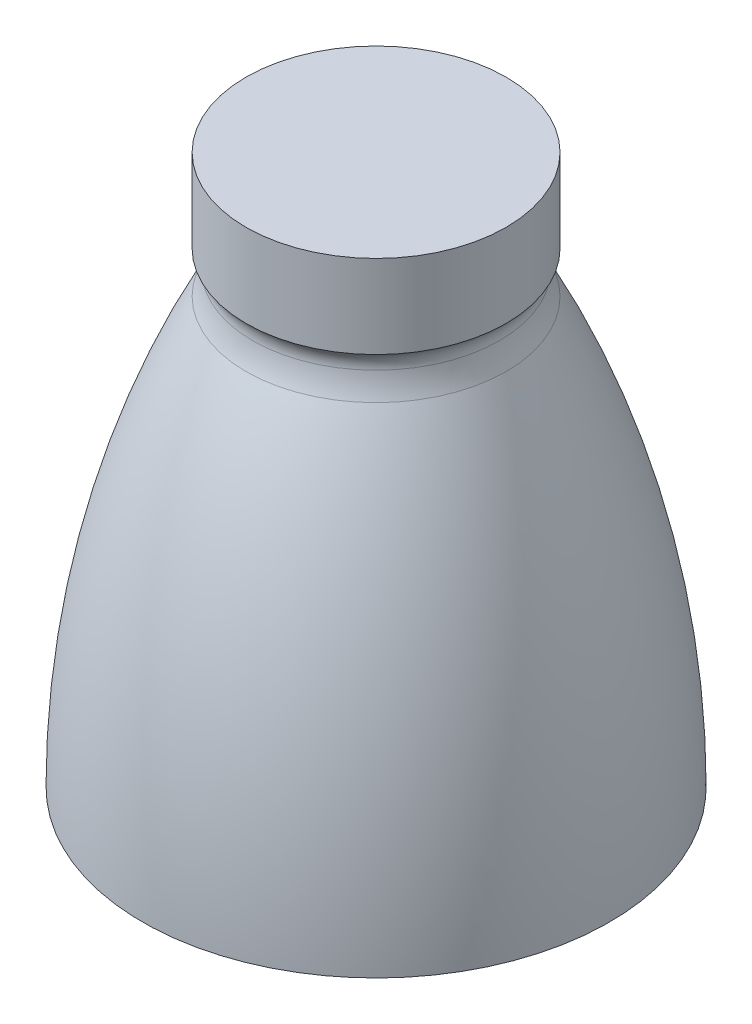
SolidWorks part; units mm, degrees
ref_plane "Front Plane" through (0, 0, 0) normal (0, 0, 1) x (1, 0, 0)
ref_plane "Top Plane" through (0, 0, 0) normal (0, 1, 0) x (1, 0, 0)
ref_plane "Right Plane" through (0, 0, 0) normal (1, 0, 0) x (0, 0, -1)
sketch "Sketch1" plane through (0, 0, 0) normal (0, 0, 1) x (1, 0, 0)
  line L0 (2.7903, 0) -> (3.125, 0)
  line L1 (0, -10.2135) -> (0, -4.4881) construction
  line L3 (5.6059, -10.2135) -> (5.1181, -10.2135)
  arc A0 (5.6059, -10.2135) -> (3.125, 0) centre (-16.6586, -10.2135) ccw
  arc A1 (5.1181, -10.2135) -> (2.7903, 0) centre (-18.4521, -10.2135) ccw
  point P10 (0, -10.2135)
  point P11 (0, 0)
revolve "Revolve1" add sketch "Sketch1" angle 360 about L1
sketch "Sketch2" plane through (0, 0, 0) normal (0, 1, 0) x (1, 0, 0)
  circle A0 centre (0, 0) radius 2.9452
extrude "Boss-Extrude1" add sketch "Sketch2" along normal blind 1 contours A0
sketch "Sketch3" plane through (0, 1, 0) normal (0, 1, 0) x (1, 0, 0)
  circle A0 centre (0, 0) radius 3.125
extrude "Boss-Extrude2" add sketch "Sketch3" along normal blind 2 contours A0
fillet "Fillet1" radius 2 1 edges at (0, 0, 2.9452)
fillet "Fillet2" radius 0.5 1 edges at (0, 1, 2.9452)
